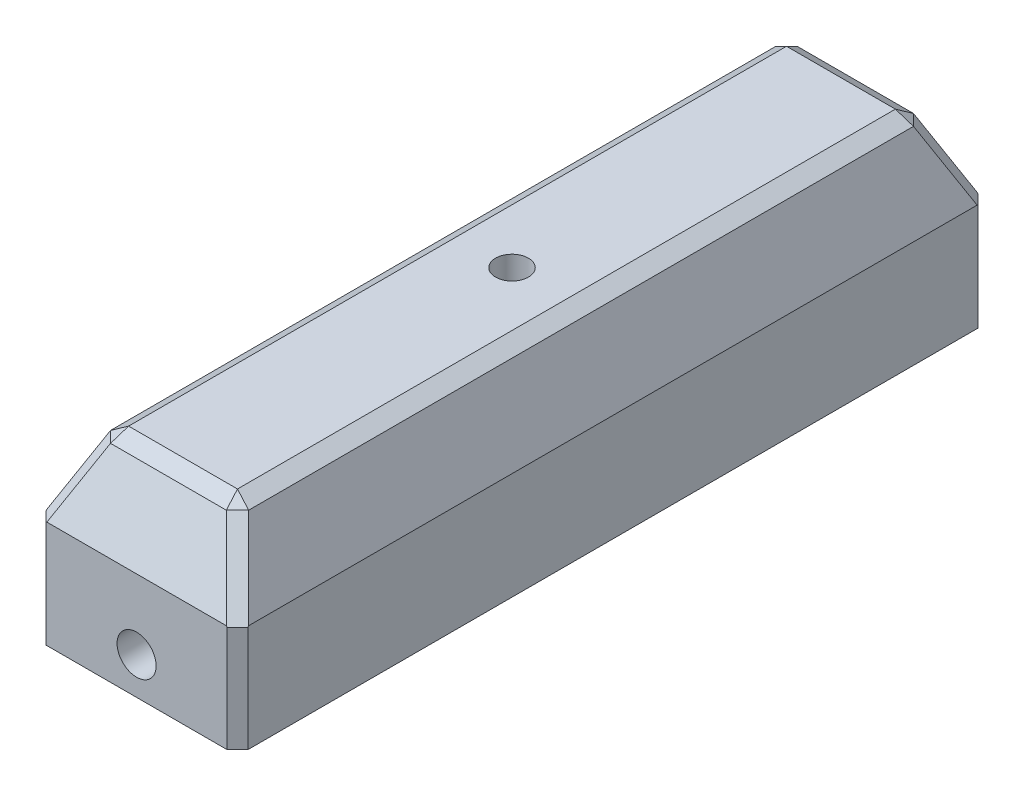
SolidWorks part; units mm, degrees
material "ABS"
ref_plane "正面" through (0, 0, 0) normal (0, 0, 1) x (1, 0, 0)
ref_plane "平面" through (0, 0, 0) normal (0, 1, 0) x (1, 0, 0)
ref_plane "右側面" through (0, 0, 0) normal (1, 0, 0) x (0, 0, -1)
sketch "ｽｹｯﾁ1" plane through (0, 0, 0) normal (0, 0, 1) x (1, 0, 0)
  line L0 (-3.4953, 0) -> (-1.5047, 0)
  line L1 (-1.5047, 0) -> (-0.9953, -1.2)
  line L2 (-0.9953, -1.2) -> (0.9953, -1.2)
  line L3 (0, 0) -> (0, -4.2434) construction
  line L4 (1.5047, 0) -> (0.9953, -1.2)
  line L5 (3.4953, 0) -> (1.5047, 0)
  line L6 (-2.5, 1.2) -> (-2.5, -0.4451) construction
  line L7 (2.5, 1.2) -> (2.5, -0.4451) construction
  line L8 (-3.4953, 0) -> (-4.0047, -1.2)
  line L9 (3.4953, 0) -> (4.0047, -1.2)
  line L10 (-4.9047, -1.2) -> (-4.0047, -1.2)
  line L11 (4.9047, -1.2) -> (4.0047, -1.2)
  line L12 (-4.9047, -1.2) -> (-4.9047, 4)
  line L13 (-4.9047, 4) -> (-3.1467, 7.77)
  line L14 (-3.1467, 7.77) -> (3.1467, 7.77)
  line L15 (3.1467, 7.77) -> (4.9047, 4)
  line L16 (4.9047, 4) -> (4.9047, -1.2)
  point P8 (0, -1.2)
  point P16 (-2.5, 0)
  point P18 (2.5, 0)
  dimension "D1" = 1.2
  dimension "D2" = 5
  dimension "D3" = 67
  dimension "D4" = 4
  dimension "D5" = 0.9
  dimension "D6" = 3.77
  dimension "D7" = 25
extrude "ﾎﾞｽ - 押し出し1" add sketch "ｽｹｯﾁ1" along normal blind 36.5
sketch "ｽｹｯﾁ2" plane through (4.9047, 0, 0) normal (1, 0, 0) x (0, 0, -1)
  line L0 (-36.5, 4) -> (-34.742, 7.77)
  line L1 (-36.5, 7.77) -> (0, 7.77) construction
  line L2 (-34.742, 7.77) -> (-36.5, 7.77)
  line L3 (-36.5, 7.77) -> (-36.5, 4)
  line L4 (-18.25, 7.77) -> (-18.25, -1.2) construction
  line L5 (-36.5, -1.2) -> (0, -1.2) construction
  line L6 (-1.758, 7.77) -> (0, 7.77)
  line L7 (0, 4) -> (-1.758, 7.77)
  line L8 (0, 7.77) -> (0, 4)
  dimension "D1" = 25
extrude "ｶｯﾄ - 押し出し1" cut sketch "ｽｹｯﾁ2" against normal through all
chamfer "面取り1" distance 0.5 12 edges at (0, 7.77, 1.758) (3.1467, 7.77, 18.25) (0, 7.77, 34.742) (-3.1467, 7.77, 18.25) (4.9047, 1.4, 36.5) (-4.9047, 1.4, 36.5) (-4.9047, 1.4, 0) (4.9047, 1.4, 0) (4.0257, 5.885, 35.621) (-4.0257, 5.885, 35.621) (-4.0257, 5.885, 0.879) (4.0257, 5.885, 0.879)
sketch "ｽｹｯﾁ3" plane through (0, 0, 36.5) normal (0, 0, 1) x (1, 0, 0)
  line L0 (-4.4047, 3.9541) -> (-4.4047, -1.2) construction
  line L1 (4.4047, -1.2) -> (-4.4047, -1.2)
  line L2 (4.4047, -1.2) -> (4.4047, 3.9541)
  line L3 (4.4047, 3.9541) -> (-4.4047, 3.9541)
  line L4 (-4.4047, -1.2) -> (-4.4047, 3.9541)
  line L5 (4.4047, -1.2) -> (-4.4047, 3.9541) construction
  line L6 (4.4047, 3.9541) -> (-4.4047, -1.2) construction
  line L8 (-4.4047, -1.2) -> (-4.0047, -1.2) construction
  point P0 (0, 1.377)
extrude "ﾎﾞｽ - 押し出し3" add sketch "ｽｹｯﾁ3" against normal blind 8.25
sketch "ｽｹｯﾁ4" plane through (0, 0, 36.5) normal (0, 0, 1) x (1, 0, 0)
  line L0 (0, 0) -> (0, -1.2) construction
  line L1 (-4.4047, -1.2) -> (4.4047, -1.2) construction
  circle A0 centre (0, 0.6) radius 0.95
  dimension "D1" = 1.8
  dimension "D2" = 1.9
extrude "ｶｯﾄ - 押し出し2" cut sketch "ｽｹｯﾁ4" against normal blind 10
ref_axis "軸1" through (0, 0.6, 26.5) along (0, 0, 1)
ref_plane "平面1" through (0, 0.6, 0) normal (0, 1, 0) x (1, 0, 0)
ref_plane "平面2" through (0, 0, 18.25) normal (0, 0, -1) x (-1, 0, 0)
mirror "ﾐﾗｰ1" about plane through (0, 0, 18.25) normal (0, 0, -1) of "ﾎﾞｽ - 押し出し3", "ｶｯﾄ - 押し出し2"
sketch "ｽｹｯﾁ5" plane through (0, 0.6, 0) normal (0, 1, 0) x (1, 0, 0)
  line L0 (0, -26.5) -> (0, -36.5) construction
  line L1 (4, -31.5) -> (0, -31.5)
  line L2 (4, -31.5) -> (4, -35)
  line L3 (4, -35) -> (0, -35)
  line L4 (0, -31.5) -> (0, -35)
  line L5 (4, -31.5) -> (0, -35) construction
  line L6 (4, -35) -> (0, -31.5) construction
  line L8 (4, -1.5) -> (0, -1.5)
  line L9 (4, -1.5) -> (4, -5)
  line L10 (4, -5) -> (0, -5)
  line L11 (0, -1.5) -> (0, -5)
  line L12 (4, -1.5) -> (0, -5) construction
  line L13 (4, -5) -> (0, -1.5) construction
  line L14 (0.9953, -28.25) -> (4.0047, -28.25) construction
  line L15 (0.9953, -8.25) -> (4.0047, -8.25) construction
  point P0 (2, -33.25)
  point P7 (2, -3.25)
  dimension "D1" = 5
  dimension "D2" = 3.5
  dimension "D3" = 4
  dimension "D4" = 5
revolve "ｶｯﾄ - 回転1" cut sketch "ｽｹｯﾁ5" angle 360 about axis through (0, 0.6, 26.5) along (0, 0, 1)
sketch "ｽｹｯﾁ6" plane through (0, 7.77, 0) normal (0, 1, 0) x (1, 0, 0)
  line L0 (0, -2.258) -> (0, -34.242) construction
  line L1 (2.6467, -2.258) -> (-2.6467, -2.258) construction
  line L2 (-2.6467, -34.242) -> (2.6467, -34.242) construction
  circle A0 centre (0, -18.25) radius 0.8
  dimension "D1" = 1.6
extrude "ｶｯﾄ - 押し出し3" cut sketch "ｽｹｯﾁ6" against normal through all
